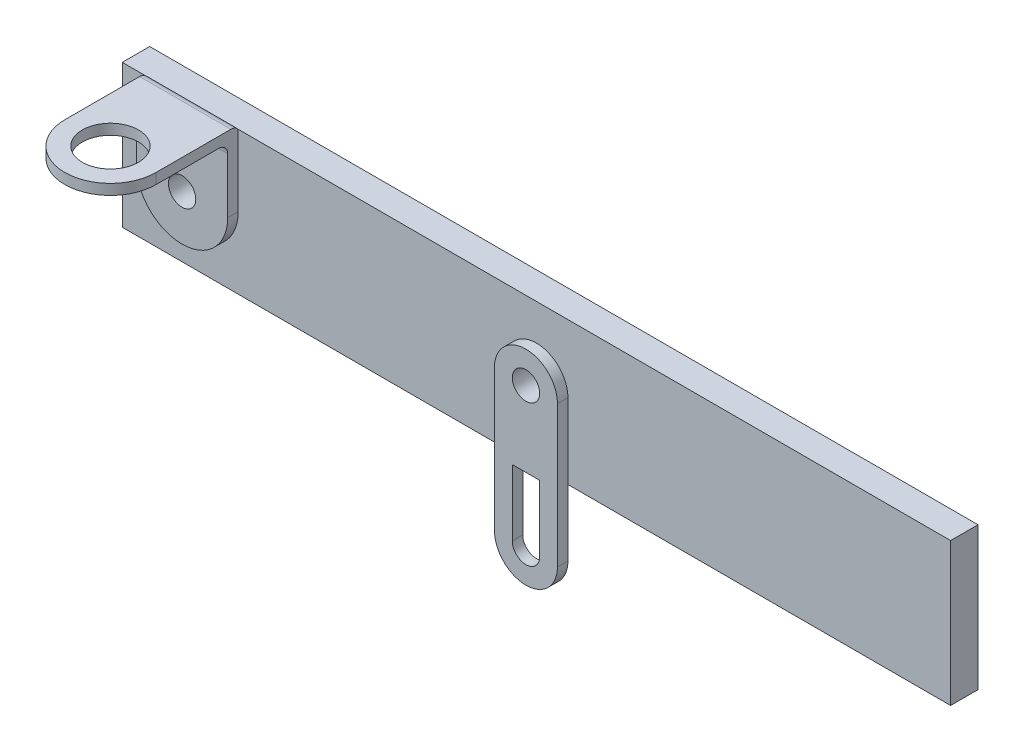
SolidWorks part; units mm, degrees
ref_plane "前基準面" through (0, 0, 0) normal (0, 0, 1) x (1, 0, 0)
ref_plane "上基準面" through (0, 0, 0) normal (0, 1, 0) x (1, 0, 0)
ref_plane "右基準面" through (0, 0, 0) normal (1, 0, 0) x (0, 0, -1)
sketch "草圖1" plane through (0, 0, 0) normal (0, 0, 1) x (1, 0, 0)
  line L0 (-23.0505, 0) -> (23.0505, 0)
  line L1 (23.0505, 0) -> (23.0505, -7.9502)
  line L2 (23.0505, -7.9502) -> (-23.0505, -7.9502)
  line L3 (-23.0505, -7.9502) -> (-23.0505, 0)
  dimension "D1" = 7.9502
  dimension "D2" = 46.101
extrude "伸長1" add sketch "草圖1" along normal blind 1.524
sketch "草圖2" plane through (0, 0, 1.524) normal (0, 0, 1) x (1, 0, 0)
  line L0 (-21.6789, -0.381) -> (-21.6789, -3.9751)
  line L1 (-16.5989, -3.9751) -> (-16.5989, -0.381)
  line L2 (-16.5989, -0.381) -> (-21.6789, -0.381)
  line L3 (23.0505, 0) -> (-23.0505, 0) construction
  line L4 (-23.0505, 0) -> (-23.0505, -7.9502) construction
  arc A0 (-21.6789, -3.9751) -> (-16.5989, -3.9751) centre (-19.1389, -3.9751) ccw
  dimension "D3" = 3.9116
  dimension "D4" = 2.54
  dimension "D1" = 3.9751
  dimension "D2" = 0.381
extrude "伸長2" add sketch "草圖2" along normal blind 0.5842
sketch "草圖3" plane through (0, -0.381, 0) normal (0, 1, 0) x (1, 0, 0)
  line L0 (-16.5989, -1.524) -> (-21.6789, -1.524) construction
  line L1 (-16.5989, -1.524) -> (-21.6789, -1.524)
  line L2 (-21.6789, -1.524) -> (-21.6789, -6.096)
  line L3 (-16.5989, -6.096) -> (-16.5989, -1.524)
  line L4 (23.0505, 0) -> (-23.0505, 0) construction
  arc A0 (-21.6789, -6.096) -> (-16.5989, -6.096) centre (-19.1389, -6.096) ccw
  circle A1 centre (-19.1389, -6.096) radius 1.5621
  dimension "D1" = 3.1242
  dimension "D2" = 6.096
extrude "伸長3" add sketch "草圖3" along normal blind 0.5842
fillet "圓角1" radius 0.508 2 edges at (-19.1389, -0.381, 2.1082) (-19.1389, 0.2032, 1.524)
sketch "草圖4" plane through (0, 0, 2.1082) normal (0, 0, 1) x (1, 0, 0)
  circle A0 centre (-19.1389, -3.9751) radius 0.762
  dimension "D1" = 1.524
extrude "伸長4" cut sketch "草圖4" against normal through all
sketch "草圖5" plane through (0, 0, 1.524) normal (0, 0, 1) x (1, 0, 0)
  line L0 (-1.7526, -11.6332) -> (-1.7526, -3.7592)
  line L1 (1.7526, -3.7592) -> (1.7526, -11.6332)
  line L2 (-0.762, -7.9502) -> (-0.762, -11.6332)
  line L3 (0.762, -11.6332) -> (0.762, -7.9502)
  line L4 (0.762, -7.9502) -> (-0.762, -7.9502)
  line L6 (-23.0505, -7.9502) -> (23.0505, -7.9502) construction
  arc A0 (-1.7526, -3.7592) -> (1.7526, -3.7592) centre (0, -3.7592) cw
  arc A1 (1.7526, -11.6332) -> (-1.7526, -11.6332) centre (0, -11.6332) cw
  arc A2 (-0.762, -11.6332) -> (0.762, -11.6332) centre (0, -11.6332) ccw
  dimension "D3" = 7.874
  dimension "D5" = 4.191
  dimension "D1" = 1.524
  dimension "D2" = 3.5052
extrude "伸長5" add sketch "草圖5" along normal blind 0.5842
sketch "草圖6" plane through (0, 0, 2.1082) normal (0, 0, 1) x (1, 0, 0)
  circle A0 centre (0, -3.7592) radius 0.762
  dimension "D1" = 1.524
extrude "伸長6" cut sketch "草圖6" against normal through all
